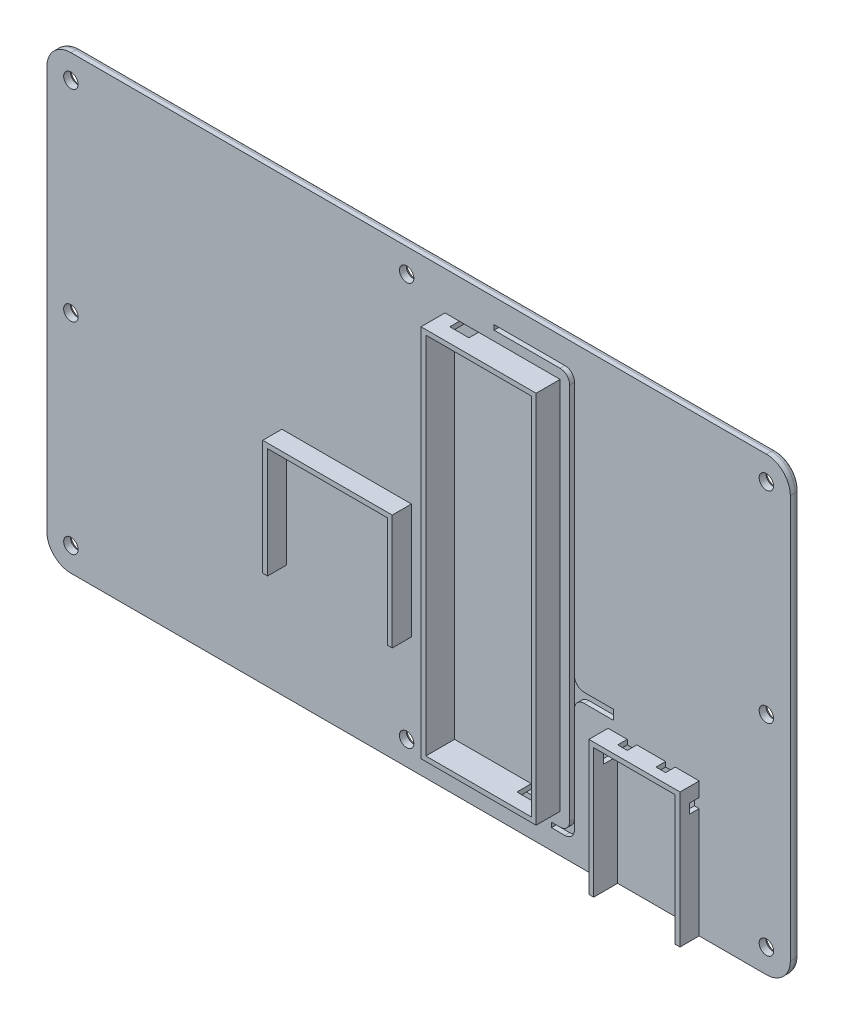
SolidWorks part; units mm, degrees
ref_plane "Front Plane" through (0, 0, 0) normal (0, 0, 1) x (1, 0, 0)
ref_plane "Top Plane" through (0, 0, 0) normal (0, 1, 0) x (1, 0, 0)
ref_plane "Right Plane" through (0, 0, 0) normal (1, 0, 0) x (0, 0, -1)
sketch "Sketch1" plane through (0, 0, 0) normal (0, 0, 1) x (1, 0, 0)
  line L1 (-70, 47) -> (75, 47)
  line L2 (-75, 42) -> (-75, -42)
  line L3 (-70, -47) -> (75, -47)
  line L4 (80, 42) -> (80, -42)
  arc A0 (75, 47) -> (80, 42) centre (75, 42) cw
  arc A1 (80, -42) -> (75, -47) centre (75, -42) cw
  arc A2 (-75, -42) -> (-70, -47) centre (-70, -42) ccw
  arc A3 (-75, 42) -> (-70, 47) centre (-70, 42) cw
  point P9 (80, -47)
  point P12 (-75, -47)
  point P15 (-75, 47)
  point P16 (0, 42)
  point P17 (-70, 42)
  point P18 (75, 0)
  point P19 (75, 42)
  point P20 (0, -42)
  point P21 (75, -42)
  point P22 (-70, 0)
  point P23 (-70, -42)
  dimension "D6" = 5
  dimension "D1" = 94
  dimension "D2" = 80
  dimension "D3" = 75
  dimension "D4" = 155
  dimension "D5" = 47
  dimension "D7" = 5
  dimension "D8" = 5
  dimension "D9" = 75
  dimension "D10" = 70
  dimension "D11" = 42
  dimension "D12" = 75
  dimension "D13" = 5
extrude "Boss-Extrude1" add sketch "Sketch1" along normal blind 2
hole_wizard "CSK for #0 Flat Head Machine Screw1" positions "Sketch7" profile "Sketch8" countersink size "#0" standard "ANSI Inch" end condition through all
sketch "Sketch7" plane through (0, 0, 0) normal (0, 0, -1) x (-1, 0, 0)
  line L0 (70, -47) -> (-75, -47) construction
  line L1 (75, 42) -> (75, -42) construction
  line L2 (-80, -42) -> (-80, 42) construction
  point P0 (-75, 42)
  point P2 (-75, 0)
  point P4 (-75, -42)
  point P6 (0, -42)
  point P8 (70, -42)
  point P10 (70, 0)
  point P12 (70, 42)
  point P14 (0, 42)
  dimension "D1" = 5
  dimension "D2" = 5
  dimension "D3" = 5
  dimension "D4" = 5
sketch "Sketch8" plane through (75, 42, 0) normal (1, 0, 0) x (0, 1, 0)
  line L0 (0, 0) -> (0, 2)
  line L1 (0, 2) -> (1.5, 2)
  line L2 (1.5, 2) -> (1.5, 0.5752)
  line L3 (1.5, 0.5752) -> (2, 0)
  line L5 (2, 0) -> (0, 0)
  line L6 (-1.5, 0.5752) -> (-2, 0) construction
  line L11 (0, -6.35) -> (0, 107.95) construction
  dimension "Thru Hole Dia." = 3
  dimension "Thru Hole Depth" = 2
  dimension "Near C'Sink Dia." = 4
  dimension "Near C'Sink Angle" = 82
fillet "Fillet1" radius 1 8 edges at (78.5355, 45.5355, 0) (80, 0, 0) (78.5355, -45.5355, 0) (2.5, -47, 0) (-73.5355, -45.5355, 0) (-75, 0, 0) (-73.5355, 45.5355, 0) (2.5, 47, 0)
sketch "Sketch9" plane through (0, 0, 2) normal (0, 0, 1) x (1, 0, 0)
  line L0 (-70, -47) -> (75, -47) construction
  line L1 (43, -47) -> (60, -47)
  line L2 (43, -47) -> (43, -20)
  line L3 (43, -20) -> (60, -20)
  line L4 (60, -47) -> (60, -20)
  line L5 (80, -42) -> (80, 42) construction
  line L6 (8, -39) -> (8, 39)
  line L7 (9, -38) -> (31, -38)
  line L8 (9, -38) -> (9, 38)
  line L9 (9, 38) -> (31, 38)
  line L10 (31, -38) -> (31, 38)
  line L11 (8, 39) -> (32, 39)
  line L12 (32, -39) -> (32, 39)
  line L13 (8, -39) -> (32, -39)
  line L14 (43, -47) -> (42, -47)
  line L15 (42, -47) -> (42, -19)
  line L16 (42, -19) -> (61, -19)
  line L17 (61, -19) -> (61, -47)
  line L18 (61, -47) -> (60, -47)
  line M18 (-70, -47) -> (75, -47)
  dimension "D1" = 27
  dimension "D2" = 17
  dimension "D3" = 20
  dimension "D4" = 76
  dimension "D5" = 22
  dimension "D6" = 9
  dimension "D7" = 12
  dimension "D9" = 1
  dimension "D10" = 1
  dimension "D11" = 1
  dimension "D8" = 1
extrude "Cut-Extrude2" cut sketch "Sketch9" against normal blind 1 contours L7 L10 L9 L8 region at (20, 0, 2)
extrude "Boss-Extrude4" add sketch "Sketch9<5>" along normal blind 5 contours L6 L13 L12 L11 L10 L7 L8 L9 region at (8.8161, 0, 2)
sketch "Sketch9<5>" plane through (0, 0, 2) normal (0, 0, 1) x (1, 0, 0) same geometry as "Sketch9"
sketch "Sketch11" plane through (0, 39, 0) normal (0, 1, 0) x (1, 0, 0)
  line L0 (11, -2) -> (11, -4)
  line L1 (8, -2) -> (32, -2) construction
  line L2 (11, -4) -> (15, -4)
  line L3 (15, -4) -> (15, -2)
  line L4 (8, -7) -> (8, -2) construction
  line L5 (11, -2) -> (15, -2)
  dimension "D1" = 4
  dimension "D2" = 2
  dimension "D3" = 3
extrude "Cut-Extrude4" cut sketch "Sketch11" against normal blind 5
sketch "Sketch13" plane through (0, -39, 0) normal (0, -1, 0) x (1, 0, 0)
  line L0 (29, 2) -> (29, 4)
  line L1 (8, 2) -> (32, 2) construction
  line L2 (29, 4) -> (25, 4)
  line L3 (25, 4) -> (25, 2)
  line L4 (25, 2) -> (29, 2)
  line L5 (32, 7) -> (32, 2) construction
  dimension "D1" = 4
  dimension "D2" = 2
  dimension "D3" = 3
extrude "Cut-Extrude5" cut sketch "Sketch13" against normal blind 1
sketch "Sketch14" plane through (0, 38, 0) normal (0, -1, 0) x (1, 0, 0)
  line L0 (11, 2) -> (11, 1)
  line L1 (9, 1) -> (31, 1) construction
  line L2 (11, 1) -> (15, 1)
  line L3 (15, 1) -> (15, 2)
  line L4 (15, 2) -> (11, 2)
extrude "Cut-Extrude6" cut sketch "Sketch14" against normal blind 1
sketch "Sketch15" plane through (0, -38, 0) normal (0, 1, 0) x (1, 0, 0)
  line L0 (29, -2) -> (29, -1)
  line L1 (9, -1) -> (31, -1) construction
  line L2 (29, -1) -> (25, -1)
  line L3 (25, -1) -> (25, -2)
  line L4 (25, -2) -> (29, -2) construction
  line L5 (25, -2) -> (29, -2)
  line L6 (25, -4) -> (25, -2) construction
extrude "Cut-Extrude7" cut sketch "Sketch15" against normal blind 1
extrude "Boss-Extrude5" add sketch "Sketch9<7>" along normal blind 4 contours L17 L16 L15 L2 L3 L4 M18 region at (42.5, -46.6616, 2)
sketch "Sketch9<7>" plane through (0, 0, 2) normal (0, 0, 1) x (1, 0, 0) same geometry as "Sketch9"
sketch "Sketch17" plane through (0, -20, 0) normal (0, -1, 0) x (1, 0, 0)
  line L0 (46, 2) -> (46, 4)
  line L1 (43, 2) -> (60, 2) construction
  line L2 (46, 4) -> (48, 4)
  line L3 (48, 4) -> (48, 2)
  line L4 (48, 2) -> (46, 2)
  line L5 (56, 2) -> (56, 4)
  line L6 (56, 4) -> (54, 4)
  line L7 (54, 4) -> (54, 2)
  line L8 (54, 2) -> (56, 2)
  line L9 (43, 6) -> (43, 2) construction
  dimension "D1" = 10
  dimension "D2" = 2
  dimension "D3" = 2
  dimension "D4" = 2
  dimension "D5" = 2
  dimension "D6" = 3
extrude "Cut-Extrude10" cut sketch "Sketch9<8>" against normal blind 1 contours L4 L3 L2 M18 region at (51.5, -33.5, 2)
sketch "Sketch9<8>" plane through (0, 0, 2) normal (0, 0, 1) x (1, 0, 0) same geometry as "Sketch9"
extrude "Cut-Extrude11" cut sketch "Sketch17" against normal blind 1
sketch "Sketch18" plane through (60, 0, 0) normal (-1, 0, 0) x (0, 0, 1)
  line L0 (2, -22) -> (2, -24)
  line L1 (2, -24) -> (4, -24)
  line L2 (4, -24) -> (4, -22)
  line L3 (4, -22) -> (2, -22)
  line L4 (6, -20) -> (1, -20) construction
  line L5 (1, -47) -> (1, -20) construction
  dimension "D1" = 2
  dimension "D2" = 2
  dimension "D3" = 1
  dimension "D4" = 2
extrude "Cut-Extrude12" cut sketch "Sketch18" against normal blind 1 and the other way blind 21
sketch "Sketch19" plane through (0, 0, 2) normal (0, 0, 1) x (1, 0, 0)
  line L1 (30.1913, -41.8498) -> (32, -41.8498)
  line L2 (34, -39.8498) -> (34, -16)
  line L8 (43.1017, -17) -> (37, -17)
  line L9 (35, -19) -> (35, -40.8498)
  line L10 (33, -42.8498) -> (30.1913, -42.8498)
  line L16 (43.1017, -16) -> (43.1017, -17)
  line L17 (30.1913, -41.8498) -> (30.1913, -42.8498)
  line L18 (18.2354, 41) -> (32, 41)
  line L19 (34, 39) -> (34, -16)
  line L21 (43.1017, -16) -> (43.1017, -15)
  line L22 (43.1017, -15) -> (37, -15)
  line L23 (35, -13) -> (35, 40)
  line L24 (33, 42) -> (18.2354, 42)
  line L25 (18.2354, 42) -> (18.2354, 41)
  line L26 (15, 39) -> (32, 39) construction
  line L27 (32, -39) -> (32, 39) construction
  line L28 (42, -19) -> (61, -19) construction
  arc A0 (33, -42.8498) -> (35, -40.8498) centre (33, -40.8498) ccw
  arc A1 (34, -39.8498) -> (32, -41.8498) centre (32, -39.8498) cw
  arc A2 (35, 40) -> (33, 42) centre (33, 40) ccw
  arc A3 (34, 39) -> (32, 41) centre (32, 39) ccw
  arc A4 (37, -15) -> (35, -13) centre (37, -13) cw
  arc A5 (35, -19) -> (37, -17) centre (37, -19) cw
  dimension "D4" = 2
  dimension "D11" = 2
  dimension "D1" = 1
  dimension "D2" = 1
  dimension "D3" = 2
  dimension "D5" = 1
  dimension "D6" = 1
  dimension "D7" = 2
  dimension "D8" = 1
  dimension "D9" = 2
  dimension "D10" = 2
  dimension "D12" = 2
extrude "Cut-Extrude13" cut sketch "Sketch19" against normal blind 1 contours L24 L25 L18 L19 L2 L1 L17 L10 L9 L8 L16 L21 L22 L23 region at (31.0957, -42.734, 2)
sketch "Sketch20" plane through (0, 0, 2) normal (0, 0, 1) x (1, 0, 0)
  line L0 (0, 0) -> (0, -23)
  line L1 (0, 0) -> (-25, 0)
  line L2 (-25, 0) -> (-25, -23)
  line L3 (8, -39) -> (8, 39) construction
  line L4 (1, 1) -> (1, -23)
  line L5 (1, 1) -> (-26, 1)
  line L6 (-26, 1) -> (-26, -23)
  line L7 (-26, -23) -> (-25, -23)
  line L8 (0, -23) -> (1, -23)
  dimension "D1" = 25
  dimension "D2" = 23
  dimension "D3" = 8
  dimension "D4" = 1
extrude "Boss-Extrude6" add sketch "Sketch20" along normal blind 4
